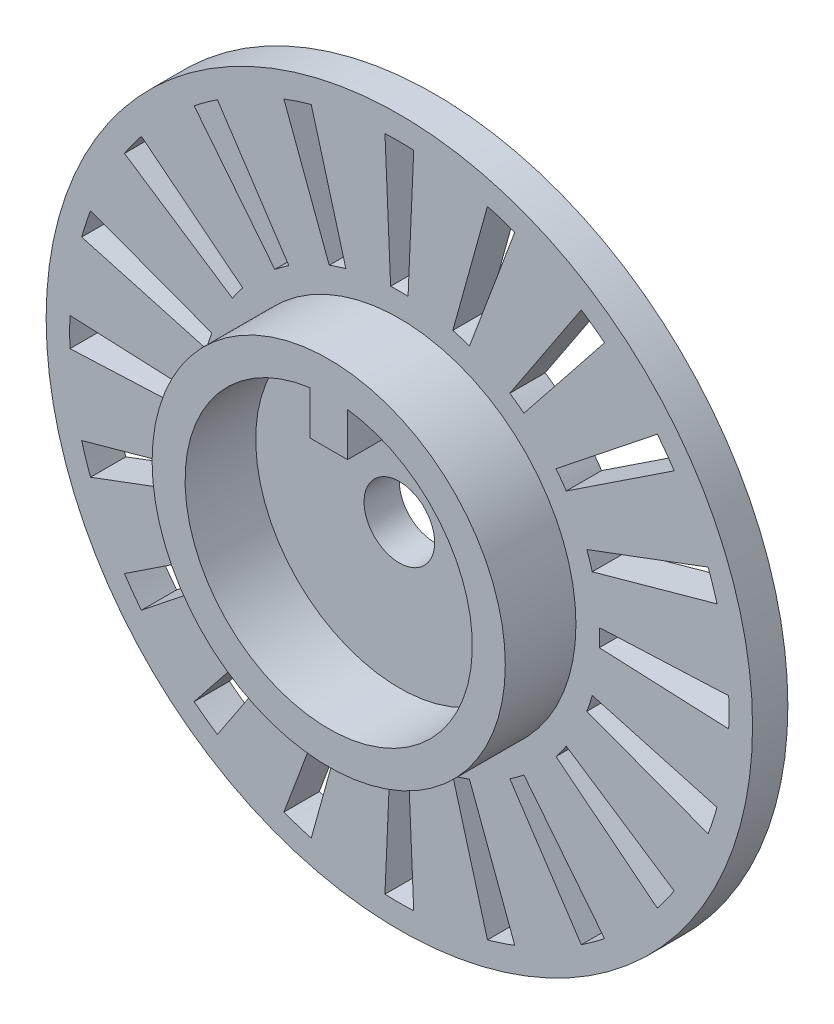
SolidWorks part; units mm, degrees
ref_plane "Plano frontal" through (0, 0, 0) normal (0, 0, 1) x (1, 0, 0)
ref_plane "Plano superior" through (0, 0, 0) normal (0, 1, 0) x (1, 0, 0)
ref_plane "Plano direito" through (0, 0, 0) normal (1, 0, 0) x (0, 0, -1)
sketch "Esboço1" plane through (0, 0, 0) normal (0, 0, 1) x (1, 0, 0)
  circle A0 centre (0, 0) radius 15
  dimension "D2" = 30
extrude "Ressalto-extrusão1" add sketch "Esboço1" along normal blind 1.5
sketch "Esboço3" plane through (0, 0, 1.5) normal (0, 0, 1) x (1, 0, 0)
  circle A0 centre (0, 0) radius 6.1
  circle A1 centre (0, 0) radius 7.5
  dimension "D1" = 12.2
  dimension "D2" = 15
extrude "Ressalto-extrusão2" add sketch "Esboço3" along normal blind 3
sketch "Esboço4" plane through (0, 0, 1.5) normal (0, 0, 1) x (1, 0, 0)
  line L1 (-0.8, 7.2) -> (0.8, 7.2)
  line L2 (-0.8, 7.2) -> (-0.8, 4.2)
  line L3 (-0.8, 4.2) -> (0.8, 4.2)
  line L4 (0.8, 7.2) -> (0.8, 4.2)
  dimension "D1" = 0.8
  dimension "D2" = 0.8
  dimension "D3" = 4.2
  dimension "D4" = 3
extrude "Ressalto-extrusão3" add sketch "Esboço4" along normal through all
sketch "Esboço5" plane through (0, 0, 1.5) normal (0, 0, 1) x (1, 0, 0)
  line L0 (0, 0) -> (0, 15) construction
  line L5 (-0.3708, 8.4919) -> (-0.6107, 13.9867)
  line L6 (0.3708, 8.4919) -> (0.6107, 13.9867)
  circle A0 centre (0, 0) radius 15 construction
  arc A1 (0.6107, 13.9867) -> (-0.6107, 13.9867) centre (0, 0) ccw
  arc A2 (0.3708, 8.4919) -> (-0.3708, 8.4919) centre (0, 0) ccw
  dimension "D3" = 28
  dimension "D4" = 17
  dimension "D1" = 2.5
  dimension "D2" = 2.5
extrude "Corte-extrusão1" cut sketch "Esboço5" against normal through all
pattern_circular "PadrãoCircular1" count 20 over 360 about axis through (0, 0, 1.5) along (0, 0, -1) of "Corte-extrusão1" reverse direction yes
sketch "Esboço7" plane through (0, 0, 1.5) normal (0, 0, 1) x (1, 0, 0)
  circle A0 centre (0, 0) radius 1.5
  dimension "D1" = 3
extrude "Corte-extrusão2" cut sketch "Esboço7" against normal through all
